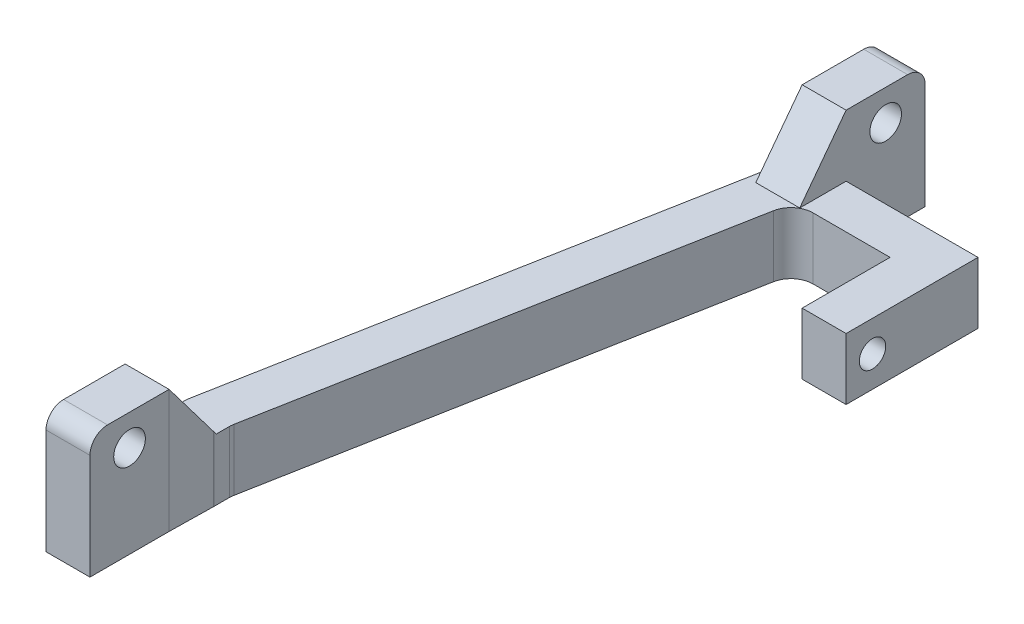
SolidWorks part; units mm, degrees
note: The reader was unsure of these and kept them because the rebuilt part matched: shared geometry of "Sketch1<3>".
material "PLA"
ref_plane "Front Plane" through (0, 0, 0) normal (0, 0, 1) x (1, 0, 0)
ref_plane "Top Plane" through (0, 0, 0) normal (0, 1, 0) x (1, 0, 0)
ref_plane "Right Plane" through (0, 0, 0) normal (1, 0, 0) x (0, 0, -1)
sketch "Sketch1" plane through (0, 0, 0) normal (0, 1, 0) x (1, 0, 0)
  line L0 (-28.5, 0) -> (-28.5, -9)
  line L1 (-28.5, -9) -> (-23.5, -9)
  line L2 (-23.5, -9) -> (-23.5, 0)
  line L3 (-23.5, 0) -> (23.5, 0)
  line L4 (23.5, 0) -> (23.5, -9)
  line L5 (23.5, -9) -> (28.5, -9)
  line L6 (28.5, -9) -> (28.5, 0)
  line L7 (28.5, 0) -> (28.5, 7)
  line L8 (28.5, 7) -> (17.5, 66)
  line L9 (17.5, 66) -> (17.5, 75)
  line L10 (17.5, 75) -> (12.5, 75)
  line L11 (12.5, 75) -> (12.5, 66)
  line L12 (12.5, 66) -> (-12.5, 66)
  line L13 (-12.5, 66) -> (-12.5, 75)
  line L14 (-12.5, 75) -> (-17.5, 75)
  line L15 (-17.5, 75) -> (-17.5, 66)
  line L16 (-17.5, 66) -> (-28.5, 7)
  line L17 (-28.5, 7) -> (-28.5, 0)
  line L18 (-13.346, 61) -> (-23.4138, 7)
  line L19 (-23.4138, 7) -> (-23.4138, 5)
  line L20 (-23.4138, 5) -> (23.4138, 5)
  line L21 (23.4138, 5) -> (23.4138, 7)
  line L22 (23.4138, 7) -> (13.346, 61)
  line L23 (13.346, 61) -> (-13.346, 61)
  line L24 (-17.5, 66) -> (-12.5, 66)
  line L25 (12.5, 66) -> (17.5, 66)
  line L26 (23.5, 0) -> (28.5, 0)
  line L27 (-23.5, 0) -> (-28.5, 0)
  line L28 (23.5, 0) -> (23.4138, 5)
  line L29 (-23.4138, 5) -> (-23.5, 0)
  point P17 (0, 0)
  point P29 (0, 66)
  dimension "D1" = 5
  dimension "D2" = 47
  dimension "D3" = 25
  dimension "D4" = 66
  dimension "D5" = 9
  dimension "D6" = 9
  dimension "D7" = 7
  dimension "D9" = 5
  dimension "D10" = 5
  dimension "D11" = 5
  dimension "D12" = 5
extrude "Boss-Extrude1" add sketch "Sketch1" along normal blind 7 contours L27 L3 L26 L7 L8 L25 L12 L24 L16 L17 L23 L22 L21 L20 L19 L18 | L2 L27 L0 L1 | L26 L4 L5 L6 | L15 L24 L13 L14 | L11 L25 L9 L10
extrude "Boss-Extrude2" add sketch "Sketch1<3>" along normal blind 7 from surface at 7 contours L15 L24 L13 L14 | L11 L25 L9 L10 | L2 L27 L0 L1 | L26 L4 L5 L6 starting at face at (0, 7, -31.2727)
sketch "Sketch1<3>" plane through (0, 0, 0) normal (0, 1, 0) x (1, 0, 0) same geometry as "Sketch1"
sketch "Sketch2" plane through (28.5, 0, 0) normal (1, 0, 0) x (0, 0, -1)
  line L0 (-9, 14) -> (0, 7) construction
  line L1 (66, 7) -> (75, 14) construction
  point P8 (70.5, 10.5)
  point P9 (-4.5, 10.5)
hole_wizard "M3 Clearance Hole1" positions "Sketch3" profile "Sketch5" hole size "M3" standard "ISO" end condition through all
sketch "Sketch3" plane through (28.5, 0, 0) normal (1, 0, 0) x (0, 0, -1)
  point P0 (-4.5, 10.5)
  point P3 (70.5, 10.5)
sketch "Sketch5" plane through (28.5, 10.5, 4.5) normal (0, 1, 0) x (0, 0, -1)
  line L0 (0, 0) -> (0, 57)
  line L1 (0, 57) -> (1.8, 57)
  line L2 (1.8, 57) -> (1.8, 0)
  line L5 (1.8, 0) -> (0, 0)
  line L11 (0, -6.35) -> (0, 107.95) construction
  dimension "Thru Hole Dia." = 3.6
  dimension "Thru Hole Depth" = 57
fillet "Fillet2" radius 2.5 10 edges at (-17.5, 3.5, -66) (17.5, 3.5, -66) (28.5, 3.5, -7) (-28.5, 3.5, -7) (13.346, 3.5, -61) (-13.346, 3.5, -61) (23.4138, 3.5, -7) (23.4138, 3.5, -5) (-23.4138, 3.5, -7) (-23.4138, 3.5, -5)
ref_plane "Plane1" through (0, 0, -61) normal (0, 0, 1) x (-1, 0, 0)
sketch "Sketch6" plane through (0, 0, -61) normal (0, 0, 1) x (1, 0, 0)
  line L1 (11.2691, 0) -> (-11.2691, 0) construction
  line L2 (-2.5, 0) -> (2.5, 0)
  line L12 (-2.5, 0) -> (-2.5, 7)
  line L13 (-2.5, 7) -> (2.5, 7)
  line L14 (2.5, 0) -> (2.5, 7)
  line L15 (11.2691, 7) -> (-11.2691, 7) construction
  point P11 (0, 0)
  dimension "D1" = 5
extrude "Boss-Extrude3" add sketch "Sketch6" along normal blind 10 and the other way up to next (5 mm away)
sketch "Sketch7" plane through (-2.5, 0, 0) normal (-1, 0, 0) x (0, 0, 1)
  line L0 (-72.9185, 3.5) -> (-67.319, 3.5) construction
  line L3 (-51, 7) -> (-51, 0) construction
  line L5 (-61, 7) -> (-51, 7) construction
  line L6 (-61, 0) -> (-51, 0) construction
  circle A0 centre (-54, 3.5) radius 1.5
  dimension "D1" = 3
  dimension "D2" = 3
extrude "Cut-Extrude1" cut sketch "Sketch7" against normal blind 10
fillet "Fillet6" radius 2 4 edges at (-26, 14, 9) (26, 14, 9) (15, 14, -75) (-15, 14, -75)
sketch "Sketch8" plane through (2.5, 0, 0) normal (1, 0, 0) x (0, 0, -1)
  line L0 (75, 12) -> (75, 0) construction
  line L1 (-9, 0) -> (75, 0)
  line L2 (-9, 0) -> (-9, 14)
  line L3 (-9, 14) -> (75, 14)
  line L4 (75, 0) -> (75, 14)
  line L5 (73, 14) -> (66, 14) construction
extrude "Cut-Extrude2" cut sketch "Sketch8" along normal through all
chamfer "Chamfer2" distance 7 angle 37 2 edges at (-26, 7, 0) (-15, 7, -66)
